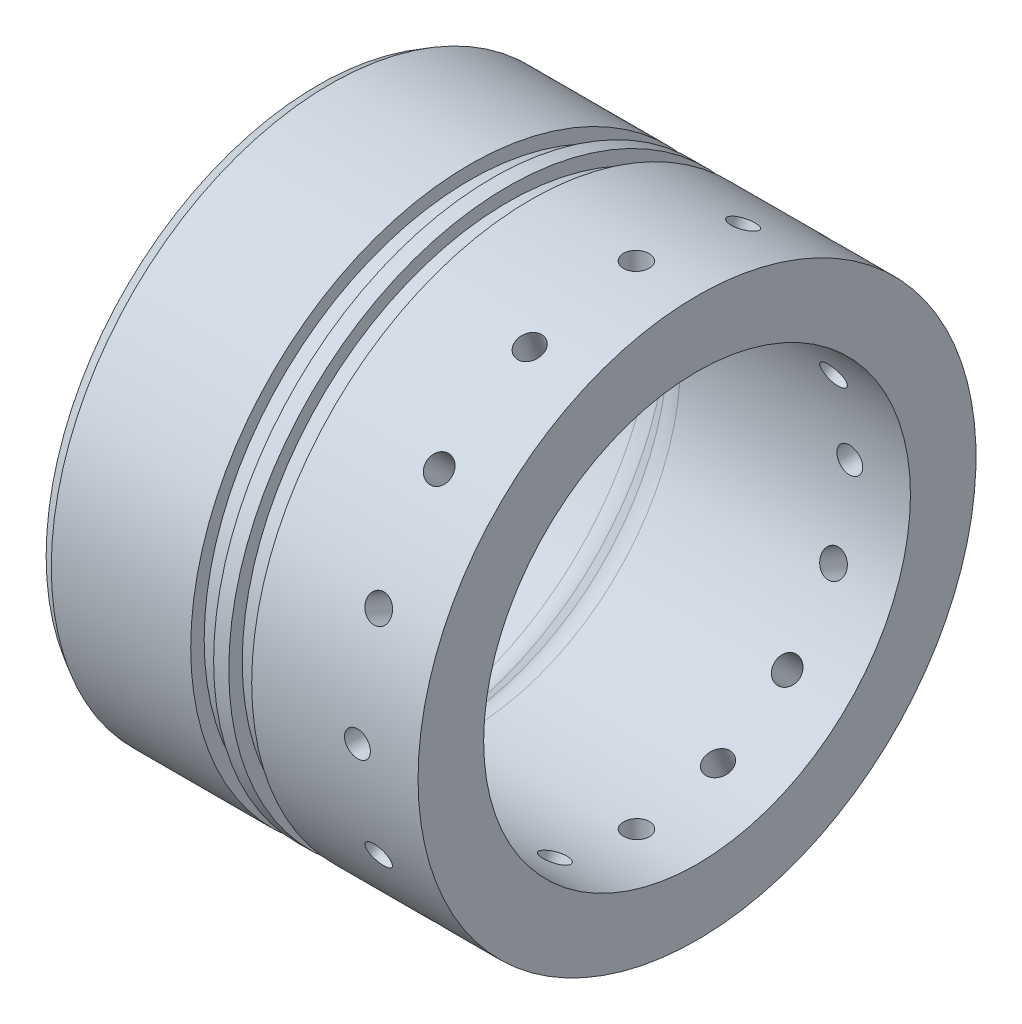
SolidWorks part; units mm, degrees
material "6061-T6 (SS)"
ref_plane "Front Plane" through (0, 0, 0) normal (0, 0, 1) x (1, 0, 0)
ref_plane "Top Plane" through (0, 0, 0) normal (0, 1, 0) x (1, 0, 0)
ref_plane "Right Plane" through (0, 0, 0) normal (1, 0, 0) x (0, 0, -1)
sketch "Sketch1" plane through (0, 0, 0) normal (0, 0, 1) x (1, 0, 0)
  line L2 (-24.8999, 4.2164) -> (-8.4802, 4.2164)
  line L12 (0, 58.4454) -> (98.3752, 58.4454) construction
  line L17 (-24.8999, 0) -> (6.8501, 0)
  line L18 (-24.8999, 4.2164) -> (-24.8999, 0)
  line L19 (-3.9901, 6.0763) -> (1.8152, 11.8815)
  line L20 (6.8501, 0) -> (6.8501, 2.8194)
  line L21 (6.8501, 2.8194) -> (11.6507, 2.8194)
  line L22 (11.6507, 2.8194) -> (11.6507, 0)
  line L23 (11.6507, 0) -> (14.8257, 0)
  line L24 (14.8257, 0) -> (14.8257, 2.8194)
  line L25 (14.8257, 2.8194) -> (19.6263, 2.8194)
  line L26 (19.6263, 2.8194) -> (19.6263, 0)
  line L27 (19.6263, 0) -> (54.4751, 0)
  line L28 (6.3053, 13.7414) -> (54.4751, 13.7414)
  line L29 (54.4751, 0) -> (54.4751, 13.7414)
  arc A0 (-3.9901, 6.0763) -> (-8.4802, 4.2164) centre (-8.4802, 10.5664) cw
  arc A1 (6.3053, 13.7414) -> (1.8152, 11.8815) centre (6.3053, 7.3914) ccw
  point P8 (-5.8499, 4.2164)
  point P22 (3.6751, 13.7414)
  dimension "D8" = 2.8194
  dimension "D9" = 54.4751
  dimension "D1" = 6.35
  dimension "D2" = 1.8152
  dimension "D3" = 3.6751
  dimension "D4" = 6.8501
  dimension "D5" = 11.6507
  dimension "D6" = 14.8257
  dimension "D7" = 3.9901
  dimension "D10" = 4.2164
  dimension "D13" = 24.8999
  dimension "D17" = 58.4454
revolve "Revolve1" add sketch "Sketch1" angle 360 about L12 region at (22.3142, 6.3808, 0)
ref_plane "Tap Reference Plane" through (0, 0, -58.4454) normal (0, 0, -1) x (-1, 0, 0)
sketch "Tap Reference" plane through (0, 0, -58.4454) normal (0, 0, -1) x (-1, 0, 0)
  line L0 (-54.4751, 58.4454) -> (-41.7751, 58.4454)
  line L1 (-54.4751, 116.8908) -> (-54.4751, 0) construction
  point P5 (-41.7751, 58.4454)
hole_wizard "Tap Drill for 1/4-28 Tap1" positions "Sketch4" profile "Sketch6" hole size "1/4-28" standard "ANSI Inch" end condition through all
sketch "Sketch4" plane through (0, 0, -58.4454) normal (0, 0, -1) x (-1, 0, 0)
  point P0 (-41.7751, 58.4454)
sketch "Sketch6" plane through (41.7751, 58.4454, -58.4454) normal (1, 0, 0) x (0, 1, 0)
  line L0 (0, 0) -> (0, 116.8908)
  line L1 (0, 116.8908) -> (2.7051, 116.8908)
  line L2 (2.7051, 116.8908) -> (2.7051, 0)
  line L5 (2.7051, 0) -> (0, 0)
  line L11 (0, -6.35) -> (0, 107.95) construction
  dimension "Thru Hole Dia." = 5.4102
  dimension "Thru Hole Depth" = 116.8908
pattern_circular "Tap Pattern" count 16 over 360 about axis through (0, 58.4454, 0) along (1, 0, 0) of "Tap Drill for 1/4-28 Tap1" reverse direction yes
chamfer "Chamfer1" distance 2.54 angle 30 1 edges at (-24.8999, 58.4454, 58.4454) first distance on face at (6.8501, 58.4454, 58.4454)
